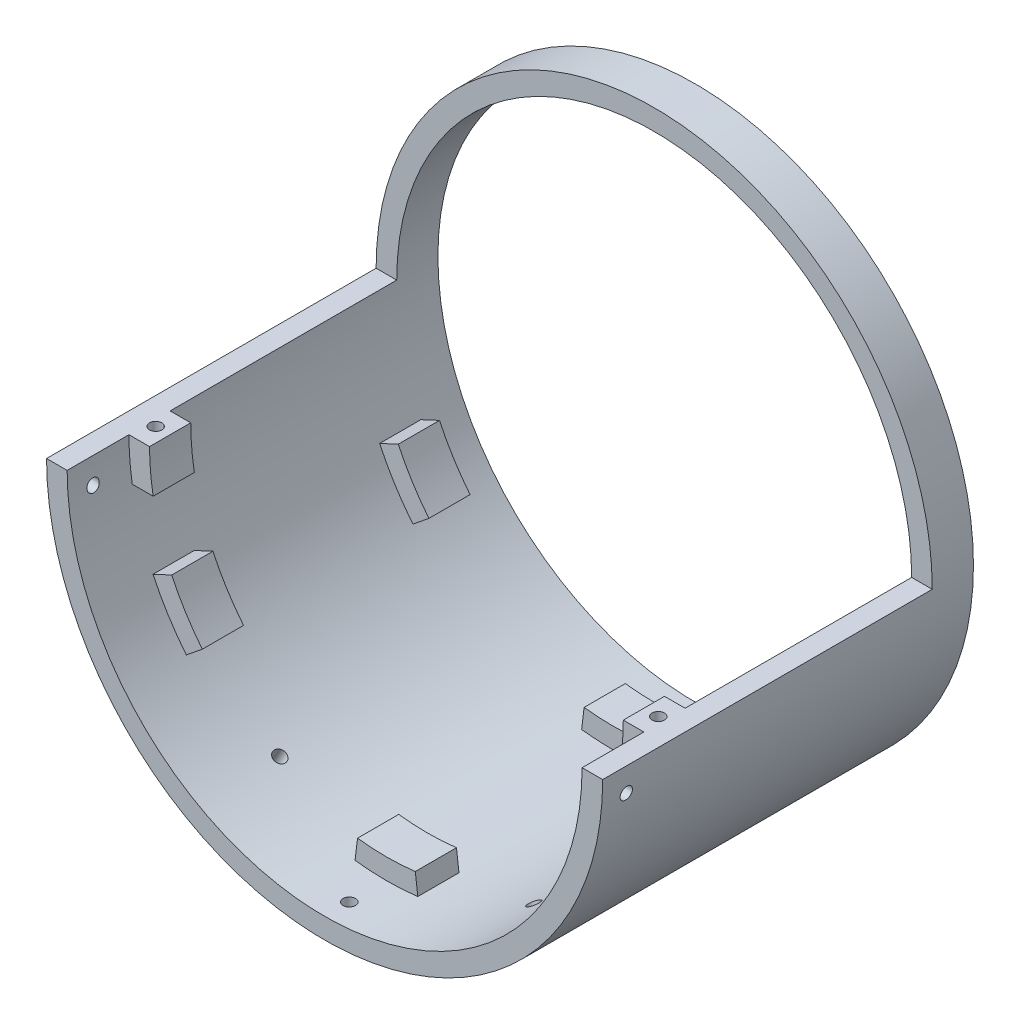
SolidWorks part; units mm, degrees
ref_plane "Front Plane" through (0, 0, 0) normal (0, 0, 1) x (1, 0, 0)
ref_plane "Top Plane" through (0, 0, 0) normal (0, 1, 0) x (1, 0, 0)
ref_plane "Right Plane" through (0, 0, 0) normal (1, 0, 0) x (0, 0, -1)
sketch "Sketch2" plane through (0, 0, 0) normal (0, 0, 1) x (1, 0, 0)
  circle A0 centre (0, 0) radius 62.5
  circle A1 centre (0, 0) radius 67.5
  dimension "D1" = 5
  dimension "D2" = 125
extrude "Boss-Extrude1" add sketch "Sketch2" along normal blind 10
sketch "Sketch3" plane through (0, 0, 10) normal (0, 0, 1) x (1, 0, 0)
  line L0 (-72.5, 0) -> (72.5, 0)
  circle A0 centre (0, 0) radius 62.5
  circle A1 centre (0, 0) radius 72.5
  circle M3 centre (0, 0) radius 67.5
  circle M4 centre (0, 0) radius 62.5
  dimension "D1" = 125
  dimension "D2" = 10
extrude "Boss-Extrude2" add sketch "Sketch3" along normal blind 80 contours L0 M3 M4 region at (65, -1.5093, 10)
sketch "Sketch6" plane through (0, 0, 10) normal (0, 0, 1) x (1, 0, 0)
  line L0 (-56.6442, -26.4136) -> (-52.1127, -24.3006)
  line L1 (-48.5716, -39.3325) -> (-44.6859, -36.1859)
  line L2 (-67.5, 0) -> (-62.5, 0) construction
  line L3 (52.1127, -24.3006) -> (56.6442, -26.4136)
  line L4 (44.6859, -36.1859) -> (48.5716, -39.3325)
  line L5 (62.5, 0) -> (67.5, 0) construction
  line L7 (7.0075, -57.0714) -> (7.6168, -62.0341)
  line L8 (-7.0075, -57.0714) -> (-7.6168, -62.0341)
  line L9 (-67.5, 0) -> (-62.5, 0) construction
  circle A0 centre (0, 0) radius 57.5
  circle A1 centre (0, 0) radius 62.5
  dimension "D1" = 115
  dimension "D2" = 5
  dimension "D3" = 14
  dimension "D4" = 25
  dimension "D5" = 14
  dimension "D6" = 25
  dimension "D7" = 83
  dimension "D8" = 14
extrude "Boss-Extrude3" add sketch "Sketch6" along normal blind 10 contours L8 A1 L7 A0 | L4 A1 L3 A0 | L0 A1 L1 A0 region at (-50.7858, -31.7345, 10) region at (50.7858, -31.7345, 10) region at (0, -59.8855, 10)
ref_plane "Plane1" through (0, 0, 65) normal (0, 0, 1) x (1, 0, 0)
sketch "Sketch11" plane through (0, 0, 65) normal (0, 0, 1) x (1, 0, 0)
  line L0 (-56.6442, -26.4136) -> (-52.1127, -24.3006)
  line L1 (-48.5716, -39.3325) -> (-44.6859, -36.1859)
  line L2 (-7.6168, -62.0341) -> (-7.0075, -57.0714)
  line L3 (7.6168, -62.0341) -> (7.0075, -57.0714)
  line L4 (48.5716, -39.3325) -> (44.6859, -36.1859)
  line L5 (56.6442, -26.4136) -> (52.1127, -24.3006)
  circle A0 centre (0, 0) radius 57.5
  circle A1 centre (0, 0) radius 62.5
  dimension "D1" = 5
  dimension "D2" = 115
extrude "Boss-Extrude5" add sketch "Sketch11" along normal blind 10 contours L4 A1 L5 A0 | L2 A1 L3 A0 | L0 A1 L1 A0 region at (-50.7858, -31.7345, 65) region at (50.7858, -31.7345, 65) region at (0, -59.8855, 65)
ref_plane "Plane2" through (62.5, 0, 0) normal (-1, 0, 0) x (0, 0, 1)
sketch "Sketch12" plane through (62.5, 0, 0) normal (-1, 0, 0) x (0, 0, 1)
  line L0 (75, 0) -> (65, 0)
  line L1 (90, 0) -> (10, 0) construction
  line L2 (65, 0) -> (65, -10)
  line L3 (65, -10) -> (75, -10)
  line L4 (75, -10) -> (75, 0)
  line L5 (75, -36.1859) -> (75, -24.3006) construction
  line L6 (65, -26.4136) -> (65, -39.3325) construction
  point P10 (70, 0)
  dimension "D1" = 10
extrude "Boss-Extrude6" add sketch "Sketch12" along normal blind 10
sketch "Sketch13" plane through (0, 0, 65) normal (0, 0, 1) x (1, 0, 0)
  circle A0 centre (0, 0) radius 57.5
  dimension "D1" = 115
ref_plane "Plane3" through (-62.5, 0, 0) normal (1, 0, 0) x (0, 0, -1)
sketch "Sketch14" plane through (-62.5, 0, 0) normal (1, 0, 0) x (0, 0, -1)
  line L1 (-65, -10) -> (-75, -10)
  line L2 (-65, -10) -> (-65, 0)
  line L3 (-65, 0) -> (-75, 0)
  line L4 (-75, -10) -> (-75, 0)
extrude "Boss-Extrude7" add sketch "Sketch14" along normal blind 10
extrude "Cut-Extrude3" cut sketch "Sketch13" against normal through all both and the other way through all
sketch "Sketch17" plane through (0, 0, 0) normal (0, 1, 0) x (1, 0, 0)
  line L0 (67.5, -90) -> (67.5, -10) construction
  line L1 (57.5, -65) -> (62.5, -65) construction
  line L3 (-57.5, -65) -> (-62.5, -65) construction
  line L4 (-67.5, -90) -> (-67.5, -10) construction
  circle A0 centre (61, -70) radius 1.5
  circle A1 centre (-61, -70) radius 1.5
  dimension "D1" = 6.5
  dimension "D2" = 3
  dimension "D3" = 5
  dimension "D4" = 3
  dimension "D5" = 5
  dimension "D6" = 6.5
extrude "Cut-Extrude4" cut sketch "Sketch17" against normal blind 6
sketch "Sketch19" plane through (62.5, 0, 0) normal (-1, 0, 0) x (0, 0, 1)
  line L0 (90, -67.5) -> (90, 0) construction
  line L1 (90, 0) -> (10, 0) construction
  circle A0 centre (84, -6) radius 1.5
  dimension "D1" = 3
  dimension "D2" = 6
  dimension "D3" = 6
extrude "Cut-Extrude5" cut sketch "Sketch19" against normal through all both and the other way through all
ref_plane "Plane4" through (0, -62.5, 0) normal (0, 1, 0) x (1, 0, 0)
sketch "Sketch20" plane through (0, -62.5, 0) normal (0, 1, 0) x (1, 0, 0)
  line L0 (-62.5, -90) -> (62.5, -90) construction
  line L2 (-62.5, -90) -> (-62.5, -75) construction
  circle A0 centre (0, -84) radius 1.5
  dimension "D1" = 6
  dimension "D2" = 3
  dimension "D3" = 62.5
extrude "Cut-Extrude8" cut sketch "Sketch20" against normal mid plane 44
ref_plane "Plane5" through (0, 0, 0) normal (0.8746, -0.4848, 0) x (0, 0, -1)
ref_plane "Plane6" through (-30.3006, -54.6637, 0) normal (0.4848, 0.8746, 0) x (0.8746, -0.4848, 0)
sketch "Sketch21" plane through (-30.3006, -54.6637, 0) normal (0.4848, 0.8746, 0) x (0.8746, -0.4848, 0)
  line L0 (-54.6637, -90) -> (62.5, -90) construction
  line L2 (-54.6637, -90) -> (-54.6637, -75) construction
  circle A0 centre (-0.6637, -70) radius 1.5
  dimension "D1" = 3
  dimension "D2" = 20
  dimension "D3" = 54
extrude "Cut-Extrude10" cut sketch "Sketch21" against normal blind 10 and the other way blind 10
ref_plane "Plane7" through (0, 0, 0) normal (0.8746, 0.4848, 0) x (0, 0, -1)
ref_plane "Plane8" through (30.3006, -54.6637, 0) normal (-0.4848, 0.8746, 0) x (0.8746, 0.4848, 0)
sketch "Sketch22" plane through (30.3006, -54.6637, 0) normal (-0.4848, 0.8746, 0) x (0.8746, 0.4848, 0)
  line L0 (-62.5, -90) -> (54.6637, -90) construction
  line L1 (21.5399, -75) -> (21.5399, -65) construction
  circle A0 centre (0.5399, -70) radius 1.5
  dimension "D1" = 3
  dimension "D2" = 20
  dimension "D3" = 21
extrude "Cut-Extrude11" cut sketch "Sketch22" against normal blind 10 and the other way blind 10
